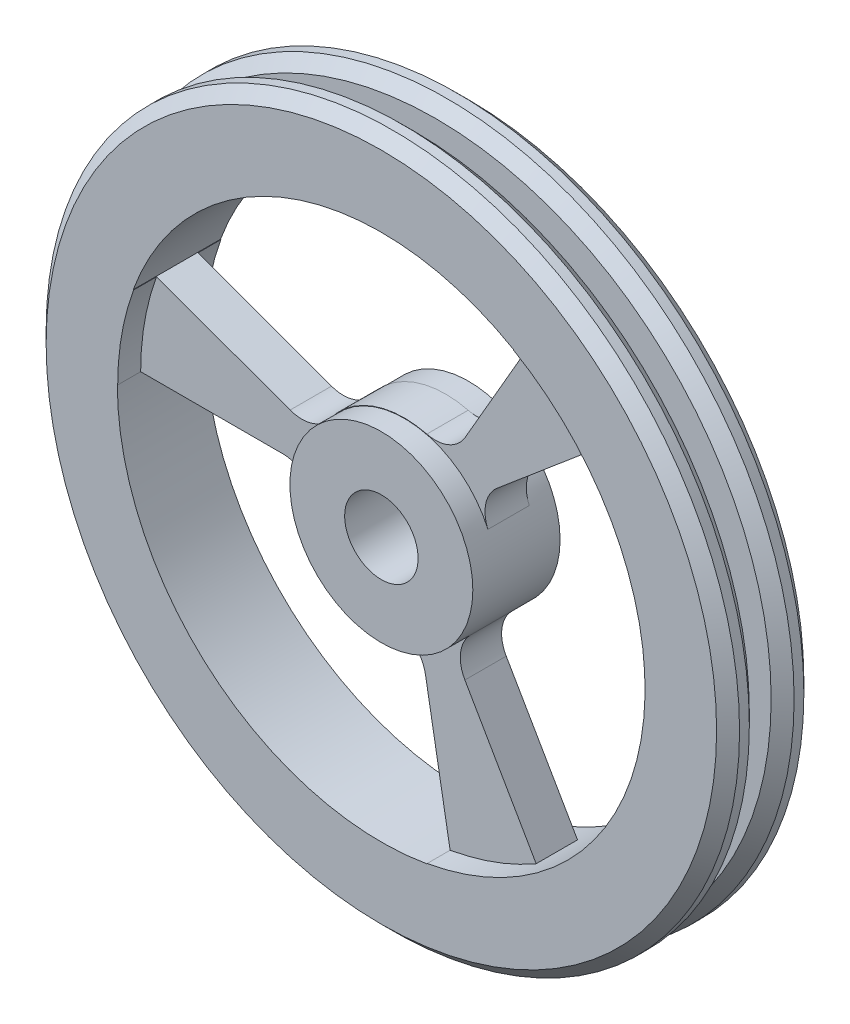
SolidWorks part; units mm, degrees
ref_plane "Front Plane" through (0, 0, 0) normal (1, 0, 0) x (0, 1, 0)
ref_plane "Top Plane" through (0, 0, 0) normal (0, 0, 1) x (0, 1, 0)
ref_plane "Right Plane" through (0, 0, 0) normal (0, 1, 0) x (-1, 0, 0)
sketch "Sketch2" plane through (0, 0, 0) normal (1, 0, 0) x (0, 1, 0)
  line L0 (0, 0) -> (0, 47.2364) construction
  line L1 (8.128, 0) -> (8.128, 19.304)
  line L2 (83.82, 0) -> (-83.82, 0) construction
  line L3 (8.128, 19.304) -> (76.708, 19.304)
  line L4 (76.708, 19.304) -> (76.708, 12.065)
  line L5 (76.708, 12.065) -> (64.008, 12.065)
  line L6 (64.008, 12.065) -> (64.008, 7.239)
  line L7 (64.008, 7.239) -> (76.708, 7.239)
  line L8 (76.708, 7.239) -> (76.708, 0)
  line L9 (76.708, 0) -> (8.128, 0)
  dimension "D1" = 8.128
  dimension "D2" = 12.7
  dimension "D3" = 68.58
  dimension "D4" = 7.239
  dimension "D5" = 7.239
  dimension "D6" = 4.826
revolve "Revolve1" add sketch "Sketch2" angle 360 about L0
chamfer "Chamfer1" distance 2.54 4 edges at (-76.708, 0, 19.304) (-76.708, 0, 12.065) (-76.708, 0, 0) (-76.708, 0, 7.239)
sketch "Sketch5" plane through (0, 0, 0) normal (0, 0, -1) x (1, 0, 0)
  line L0 (-58.42, 0) -> (-20.32, 0)
  line L1 (-10.6172, 0) -> (10.6172, 0) construction
  line L3 (29.21, -50.5932) -> (10.16, -17.5976)
  line L4 (10.1445, 57.5325) -> (3.5285, 20.0113)
  line L5 (-54.8968, -19.9808) -> (-19.0946, -6.9498)
  line L6 (15.5726, -12.9213) -> (44.6874, -37.4972)
  line L7 (29.1676, 50.5198) -> (10.1176, 17.5242)
  arc A0 (-58.42, 0) -> (10.1445, 57.5325) centre (0, 0) cw
  arc A1 (3.5285, 20.0113) -> (-20.32, 0) centre (0, 0) ccw
  arc A2 (-54.8968, -19.9808) -> (29.21, -50.5932) centre (0, 0) ccw
  arc A3 (10.16, -17.5976) -> (-19.0946, -6.9498) centre (0, 0) cw
  arc A4 (44.6874, -37.4972) -> (29.1676, 50.5198) centre (0, 0) ccw
  arc A5 (10.1176, 17.5242) -> (15.5726, -12.9213) centre (0, 0) cw
  dimension "D1" = 58.42
  dimension "D7" = 58.42
  dimension "D5" = 100
  dimension "D2" = 100
  dimension "D3" = 100
  dimension "D4" = 38.1
  dimension "D6" = 38.1
  dimension "D9" = 38.1
extrude "Cut-Extrude1" cut sketch "Sketch5" against normal through all
sketch "Sketch6" plane through (0, 0, 0) normal (0, 0, -1) x (1, 0, 0)
  circle A0 centre (0, 0) radius 58.3352
  circle A1 centre (0, 0) radius 20.2352
extrude "Cut-Extrude2" cut sketch "Sketch6" against normal blind 5.08
sketch "Sketch7" plane through (0, 0, 19.304) normal (0, 0, 1) x (0, -1, 0)
  circle A0 centre (0, 0) radius 58.3352
  circle A1 centre (0, 0) radius 20.2352
extrude "Cut-Extrude3" cut sketch "Sketch7" against normal blind 5.08
fillet "Fillet15" radius 7.62 6 edges at (10.16, 17.5976, 9.652) (-19.0946, 6.9498, 9.652) (-20.32, 0, 9.652) (3.5285, -20.0113, 9.652) (10.1176, -17.5242, 9.652) (15.5726, 12.9213, 9.652)
sketch "Sketch8" plane through (0, 0, 19.304) normal (0, 0, 1) x (0, -1, 0)
  circle A0 centre (0, 0) radius 15.24
  circle A1 centre (0, 0) radius 76.708
  dimension "D1" = 30.48
extrude "Cut-Extrude4" [suppressed] cut sketch "Sketch8" against normal through all
